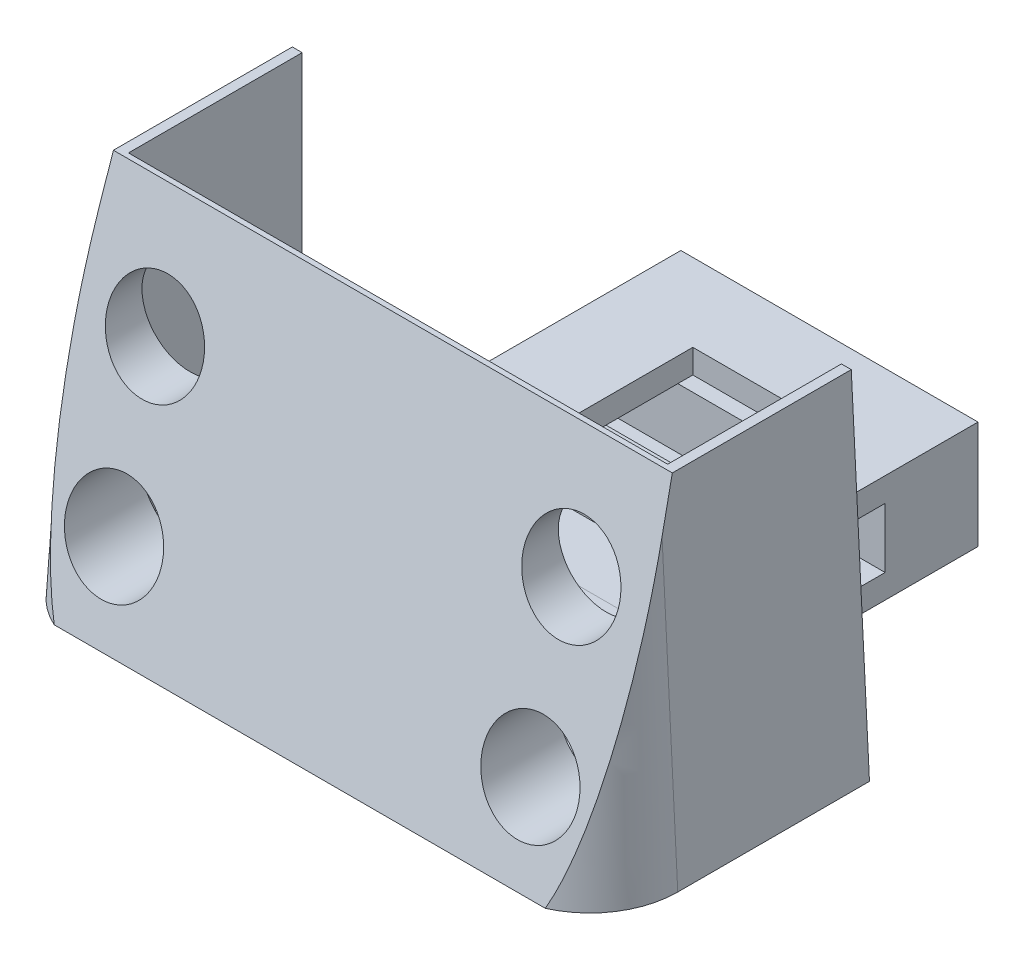
SolidWorks part; units mm, degrees
material "PLA (3D Printing)"
ref_plane "Front Plane" through (0, 0, 0) normal (0, 0, 1) x (1, 0, 0)
ref_plane "Top Plane" through (0, 0, 0) normal (0, 1, 0) x (1, 0, 0)
ref_plane "Right Plane" through (0, 0, 0) normal (1, 0, 0) x (0, 0, -1)
sketch "Sketch1" plane through (0, 0, 0) normal (0, 1, 0) x (1, 0, 0)
  line L0 (-35, 50) -> (35, 50)
  line L5 (50, 35) -> (50, -35)
  line L6 (-50, 35) -> (-50, -35)
  line L7 (-35, -50) -> (35, -50)
  arc A0 (35, -50) -> (50, -35) centre (35, -35) ccw
  arc A1 (-50, -35) -> (-35, -50) centre (-35, -35) ccw
  arc A2 (-50, 35) -> (-35, 50) centre (-35, 35) cw
  arc A3 (35, 50) -> (50, 35) centre (35, 35) cw
  point P14 (0, -50)
  point P19 (-50, 0)
  dimension "D3" = 15
  dimension "D4" = 15
  dimension "D5" = 15
  dimension "D6" = 15
  dimension "D1" = 100
  dimension "D2" = 100
extrude "Boss-Extrude1" add sketch "Sketch1" along normal blind 10
sketch "Sketch2" plane through (0, 10, 0) normal (0, 1, 0) x (1, 0, 0)
  line L0 (-50, 35) -> (-50, -35) construction
  line L1 (-42, 40) -> (-24.8, 40)
  line L2 (-42, 40) -> (-42, -3)
  line L3 (-42, -3) -> (-24.8, -3)
  line L4 (-24.8, 40) -> (-24.8, -3)
  line L5 (-42, 40) -> (-24.8, -3) construction
  line L6 (-42, -3) -> (-24.8, 40) construction
  line L7 (24.8, 40) -> (42, 40)
  line L8 (24.8, 40) -> (24.8, -3)
  line L9 (24.8, -3) -> (42, -3)
  line L10 (42, 40) -> (42, -3)
  line L11 (24.8, 40) -> (42, -3) construction
  line L12 (24.8, -3) -> (42, 40) construction
  line L13 (50, -35) -> (50, 35) construction
  line L15 (35, 50) -> (-35, 50) construction
  point P0 (-33.4, 18.5)
  point P5 (33.4, 18.5)
  dimension "D1" = 8
  dimension "D2" = 8
  dimension "D3" = 17.2
  dimension "D4" = 17.2
  dimension "D5" = 43
  dimension "D6" = 43
  dimension "D7" = 10
  dimension "D8" = 10
extrude "Cut-Extrude1" cut sketch "Sketch2" against normal through all
sketch "Sketch3" plane through (0, 10, 0) normal (0, 1, 0) x (1, 0, 0)
  line L1 (-40, -8) -> (40, -8)
  line L2 (-40, -8) -> (-40, -32)
  line L3 (-40, -32) -> (40, -32)
  line L4 (40, -8) -> (40, -32)
  line L5 (-40, -8) -> (40, -32) construction
  line L6 (-40, -32) -> (40, -8) construction
  line L7 (-45, -3) -> (45, -3)
  line L8 (-45, -3) -> (-45, -37)
  line L9 (-45, -37) -> (45, -37)
  line L10 (45, -3) -> (45, -37)
  line L11 (-45, -3) -> (45, -37) construction
  line L12 (-45, -37) -> (45, -3) construction
  line L13 (-35, -50) -> (35, -50) construction
  line L14 (-42, -3) -> (-24.8, -3) construction
  point P0 (0, -20)
  point P5 (0, -20)
  point P18 (0, -50)
  dimension "D1" = 24
  dimension "D2" = 80
  dimension "D3" = 34
  dimension "D4" = 90
extrude "Boss-Extrude3" add sketch "Sketch3" along normal blind 15
sketch "Sketch4" plane through (0, 10, 0) normal (0, 1, 0) x (1, 0, 0)
  line L0 (24.8, 40) -> (24.8, -3) construction
  line L3 (-24.8, 12.5) -> (24.8, 12.5)
  line L5 (-24.8, 24.5) -> (24.8, 24.5)
  line L6 (-24.8, 29.5) -> (24.8, 29.5)
  line L11 (-24.8, 7.5) -> (24.8, 7.5)
  line L12 (-24.8, 29.5) -> (-24.8, 24.5)
  line L13 (-24.8, -3) -> (-24.8, 40) construction
  line L14 (-24.8, 12.5) -> (-24.8, 7.5)
  line L15 (24.8, 12.5) -> (24.8, 7.5)
  line L16 (24.8, 29.5) -> (24.8, 24.5)
  point P4 (-24.8, 18.5)
  dimension "D1" = 5
  dimension "D2" = 12
  dimension "D3" = 5
  dimension "D4" = 6
extrude "Boss-Extrude4" add sketch "Sketch4" along normal blind 10
sketch "Sketch5" plane through (0, 20, 0) normal (0, 1, 0) x (1, 0, 0)
  line L0 (-24.8, 7.5) -> (24.8, 7.5) construction
  line L1 (-24.8, 29.5) -> (-9.8, 29.5)
  line L2 (-24.8, 29.5) -> (-24.8, 7.5)
  line L3 (-24.8, 7.5) -> (-9.8, 7.5)
  line L4 (-9.8, 29.5) -> (-9.8, 7.5)
  line L6 (24.8, 29.5) -> (9.8, 29.5)
  line L7 (24.8, 29.5) -> (24.8, 7.5)
  line L8 (24.8, 7.5) -> (9.8, 7.5)
  line L9 (9.8, 29.5) -> (9.8, 7.5)
  dimension "D1" = 15
  dimension "D2" = 15
extrude "Boss-Extrude5" add sketch "Sketch5" along normal blind 5
sketch "Sketch6" plane through (0, 10, 0) normal (0, 1, 0) x (1, 0, 0)
  line L1 (-45, -37) -> (45, -37)
  line L2 (-45, -37) -> (-45, 40)
  line L3 (-45, 40) -> (45, 40)
  line L4 (45, -37) -> (45, 40)
  line L5 (45, -37) -> (45, -3) construction
  line L6 (-24.8, 40) -> (-42, 40) construction
  line L7 (-50, 35) -> (-50, -35) construction
  line L8 (-35, -50) -> (35, -50) construction
  line L9 (50, -35) -> (50, 35) construction
  line L10 (35, 50) -> (-35, 50) construction
  line L11 (-50, 35) -> (-50, -35)
  line L12 (-35, -50) -> (35, -50)
  line L13 (50, -35) -> (50, 35)
  line L14 (35, 50) -> (-35, 50)
  arc A0 (-50, -35) -> (-35, -50) centre (-35, -35) ccw construction
  arc A1 (35, -50) -> (50, -35) centre (35, -35) ccw construction
  arc A2 (50, 35) -> (35, 50) centre (35, 35) ccw construction
  arc A3 (-35, 50) -> (-50, 35) centre (-35, 35) ccw construction
  arc A4 (-50, -35) -> (-35, -50) centre (-35, -35) ccw
  arc A5 (35, -50) -> (50, -35) centre (35, -35) ccw
  arc A6 (50, 35) -> (35, 50) centre (35, 35) ccw
  arc A7 (-35, 50) -> (-50, 35) centre (-35, 35) ccw
extrude "Boss-Extrude6" add sketch "Sketch6" along normal up to surface (15 mm away) up to face at (0, 25, 20)
sketch "Sketch9" plane through (0, 25, 0) normal (0, 1, 0) x (1, 0, 0)
  line L22 (-50, 35) -> (-50, -35) construction
  line L23 (-35, -50) -> (35, -50) construction
  line L24 (50, -35) -> (50, 35) construction
  line L25 (35, 50) -> (-35, 50) construction
  line L26 (-45, 35) -> (-45, -35)
  line L27 (-35, -45) -> (35, -45)
  line L28 (45, -35) -> (45, 35)
  line L29 (35, 45) -> (-35, 45)
  line L30 (-45, 35) -> (-45, -32)
  line L32 (45, -32) -> (45, 35)
  line L34 (-50, 35) -> (-50, -35)
  line L35 (-35, -50) -> (35, -50)
  line L36 (50, -35) -> (50, 35)
  line L37 (35, 50) -> (-35, 50)
  line L38 (45, -32) -> (-45, -32)
  line L39 (-40, -32) -> (40, -32) construction
  line L40 (43.6603, 40) -> (-43.6603, 40)
  line L41 (45, 40) -> (-45, 40) construction
  arc A23 (-50, -35) -> (-35, -50) centre (-35, -35) ccw construction
  arc A24 (35, -50) -> (50, -35) centre (35, -35) ccw construction
  arc A25 (50, 35) -> (35, 50) centre (35, 35) ccw construction
  arc A26 (-35, 50) -> (-50, 35) centre (-35, 35) ccw construction
  arc A27 (-45, -35) -> (-35, -45) centre (-35, -35) ccw
  arc A28 (35, -45) -> (45, -35) centre (35, -35) ccw
  arc A29 (45, 35) -> (35, 45) centre (35, 35) ccw
  arc A30 (-35, 45) -> (-45, 35) centre (-35, 35) ccw
  arc A33 (45, 35) -> (43.6603, 40) centre (35, 35) ccw
  arc A34 (-43.6603, 40) -> (-45, 35) centre (-35, 35) ccw
  arc A35 (-50, -35) -> (-35, -50) centre (-35, -35) ccw
  arc A36 (35, -50) -> (50, -35) centre (35, -35) ccw
  arc A37 (50, 35) -> (35, 50) centre (35, 35) ccw
  arc A38 (-35, 50) -> (-50, 35) centre (-35, 35) ccw
  dimension "D1" = 5
extrude "Boss-Extrude8" add sketch "Sketch9" along normal blind 39
chamfer "Chamfer1" distance 64 angle 3 8 edges at (0, 64, 50) (45.6066, 64, 45.6066) (-45.6066, 64, 45.6066) (50, 64, 0) (-50, 64, 0) (45.6066, 64, -45.6066) (-45.6066, 64, -45.6066) (0, 64, -50) first distance on face at (0, 32, 50) first distance on face at (44.0533, 32, 44.0533) first distance on face at (-44.0533, 32, 44.0533) first distance on face at (50, 32, 0) first distance on face at (-50, 32, 0) first distance on face at (44.0533, 32, -44.0533) first distance on face at (-44.0533, 32, -44.0533) first distance on face at (0, 32, -50)
chamfer "Chamfer3" distance 64 angle 12 1 edges at (0, 64, 46.6459) tangent propagation no first distance on face at (0, 32, 48.323)
sketch "Sketch17" plane through (0, 0, -29.5) normal (0, 0, -1) x (-1, 0, 0)
  line L8 (-9.8, 25) -> (-24.8, 25)
  line L9 (-24.8, 10) -> (24.8, 10)
  line L10 (-24.8, 10) -> (24.8, 10)
  line L11 (24.8, 10) -> (24.8, 25)
  line L12 (24.8, 25) -> (9.8, 25)
  line L13 (9.8, 25) -> (9.8, 20)
  line L14 (9.8, 20) -> (-9.8, 20)
  line L15 (-9.8, 20) -> (-9.8, 25)
  line L16 (-9.8, 25) -> (-24.8, 25)
  line L20 (24.8, 25) -> (9.8, 25)
  line L21 (9.8, 25) -> (9.8, 20)
  line L22 (9.8, 20) -> (-9.8, 20)
  line L23 (-9.8, 20) -> (-9.8, 25)
  line L24 (24.8, 10) -> (24.8, 25)
  line L25 (-24.8, 25) -> (-24.8, 10)
  line L26 (-24.8, 25) -> (-24.8, 10)
  dimension "D1" = 0
extrude "Cut-Extrude6" cut sketch "Sketch17" against normal blind 2.5
sketch "Sketch20" plane through (0, 25, 0) normal (0, -1, 0) x (1, 0, 0)
  line L0 (-45, -35) -> (-45, -40) construction
  line L1 (-45, -40) -> (-43.6603, -40) construction
  line L2 (45, -40) -> (45, -35) construction
  line L3 (43.6603, -40) -> (45, -40) construction
  line L4 (-45, -35) -> (-45, -40)
  line L5 (-45, -40) -> (-43.6603, -40)
  line L6 (45, -40) -> (45, -35)
  line L7 (43.6603, -40) -> (45, -40)
  arc A0 (-45, -35) -> (-43.6603, -40) centre (-35, -35) ccw construction
  arc A1 (43.6603, -40) -> (45, -35) centre (35, -35) ccw construction
  arc A2 (-45, -35) -> (-43.6603, -40) centre (-35, -35) ccw
  arc A3 (43.6603, -40) -> (45, -35) centre (35, -35) ccw
extrude "Cut-Extrude8" cut sketch "Sketch20" against normal blind 15
sketch "Sketch21" plane through (0, 25, 0) normal (0, 1, 0) x (1, 0, 0)
  line L4 (40, -8) -> (40, -32)
  line L6 (40, -8) -> (40, -32)
  line L8 (40, -32) -> (45, -32)
  line L10 (40, -32) -> (45, -32)
  line L24 (45, -32) -> (45, -3)
  line L25 (45, -32) -> (45, -3)
  line L26 (45, -3) -> (-45, -3)
  line L27 (45, -3) -> (-45, -3)
  line L28 (-45, -3) -> (-45, -32)
  line L29 (-45, -3) -> (-45, -32)
  line L30 (-45, -32) -> (-40, -32)
  line L31 (-45, -32) -> (-40, -32)
  line L32 (-40, -32) -> (-40, -8)
  line L33 (-40, -32) -> (-40, -8)
  line L34 (-40, -8) -> (40, -8)
  line L35 (-40, -8) -> (40, -8)
  dimension "D1" = 0
extrude "Cut-Extrude9" cut sketch "Sketch21" against normal up to surface (15 mm away) up to face at (0, 10, 20)
sketch "Sketch22" plane through (0, 0, 0) normal (0, -1, 0) x (1, 0, 0)
  line L0 (-35, 50) -> (35, 50) construction
  line L1 (-15, 32) -> (15, 32)
  line L2 (-15, 32) -> (-15, 25)
  line L3 (-15, 25) -> (15, 25)
  line L4 (15, 32) -> (15, 25)
  line L5 (24.8, 3) -> (42, 3) construction
  line L7 (0, 50) -> (0, -50) construction
  line L8 (35, -50) -> (-35, -50) construction
  point P12 (0, 32)
  dimension "D1" = 18
  dimension "D2" = 22
  dimension "D3" = 30
extrude "Cut-Extrude10" cut sketch "Sketch22" against normal up to surface (10 mm away) up to face at (0, 10, -18.5)
sketch "Sketch25" plane through (0, 0, 32) normal (0, 0, -1) x (-1, 0, 0)
  line L0 (-15, 10) -> (-45, 10) construction
  line L1 (45, 10) -> (15, 10) construction
  line L2 (-45, 64) -> (-45, 10) construction
  line L3 (45, 64) -> (45, 10) construction
  circle A0 centre (-34.75, 45.5) radius 8
  circle A1 centre (34.75, 45.5) radius 8
  circle A2 centre (-34.75, 20) radius 8
  circle A3 centre (34.75, 20) radius 8
  dimension "D3" = 16
  dimension "D4" = 16
  dimension "D5" = 16
  dimension "D6" = 16
  dimension "D9" = 10.25
  dimension "D1" = 25.5
  dimension "D2" = 25.5
  dimension "D7" = 10
  dimension "D8" = 10
  dimension "D10" = 10.25
extrude "Cut-Extrude19" cut sketch "Sketch25" against normal through all
sketch "Sketch29" plane through (0, 10, 0) normal (0, 1, 0) x (1, 0, 0)
  line L1 (-24, -3) -> (-15, -3)
  line L2 (-24, -3) -> (-24, -32)
  line L3 (-24, -32) -> (-15, -32)
  line L4 (-15, -3) -> (-15, -32)
  line L5 (15, -32) -> (24, -32)
  line L6 (15, -32) -> (15, -3)
  line L7 (15, -3) -> (24, -3)
  line L8 (24, -32) -> (24, -3)
  line L9 (-45, 40) -> (-45, -32) construction
  line L10 (45, -32) -> (45, 40) construction
  line L11 (-24.8, -3) -> (-42, -3) construction
  line L12 (42, -3) -> (24.8, -3) construction
  line L13 (-45, -32) -> (45, -32) construction
  dimension "D1" = 21
  dimension "D2" = 21
  dimension "D3" = 9
  dimension "D4" = 9
extrude "Boss-Extrude10" add sketch "Sketch29" along normal blind 28
sketch "Sketch31" plane through (0, 10, 0) normal (0, 1, 0) x (1, 0, 0)
  line L4 (24.8, 27) -> (24.8, 40)
  line L6 (24.8, 27) -> (24.8, 40)
  line L13 (24.8, 40) -> (-24.8, 40)
  line L15 (24.8, 40) -> (-24.8, 40)
  line L17 (-24.8, 40) -> (-24.8, 27)
  line L18 (-24.8, 40) -> (-24.8, 27)
  line L19 (-24.8, 27) -> (24.8, 27)
  line L21 (-24.8, 27) -> (24.8, 27)
  dimension "D1" = 0
extrude "Boss-Extrude12" add sketch "Sketch31" along normal up to surface (28 mm away) up to face at (-19.5, 38, 17.5)
sketch "Sketch30" plane through (0, 38, 0) normal (0, 1, 0) x (1, 0, 0)
  line L1 (-24.8, 36) -> (24.8, 36)
  line L2 (-24.8, 36) -> (-24.8, 40)
  line L3 (-24.8, 40) -> (24.8, 40)
  line L11 (-24, -3) -> (-24, -32) construction
  line L12 (-24, -22) -> (24, -22)
  line L13 (-24, -22) -> (-24, -18)
  line L14 (-24, -18) -> (24, -18)
  line L15 (24, -22) -> (24, -18)
  line L16 (24, -3) -> (24, -32) construction
  line L21 (43.6603, 40) -> (-43.6603, 40) construction
  line L22 (-24.8, 40) -> (-24.8, 27) construction
  line L23 (24.8, 40) -> (24.8, 36)
  line L24 (24.8, 27) -> (24.8, 40) construction
  dimension "D1" = 54
  dimension "D2" = 4
  dimension "D3" = 4
extrude "Boss-Extrude11" add sketch "Sketch30" along normal blind 10
sketch "Sketch33" plane through (0, 25, 0) normal (0, 1, 0) x (1, 0, 0)
  line L0 (24.8, 27) -> (9.8, 27) construction
  line L1 (9.8, 27) -> (9.8, 7.5) construction
  line L2 (9.8, 7.5) -> (24.8, 7.5) construction
  line L3 (24.8, 7.5) -> (24.8, 27) construction
  line L4 (-9.8, 7.5) -> (-9.8, 27) construction
  line L5 (-9.8, 27) -> (-24.8, 27) construction
  line L6 (-24.8, 27) -> (-24.8, 7.5) construction
  line L7 (-24.8, 7.5) -> (-9.8, 7.5) construction
  line L8 (24.8, 27) -> (9.8, 27)
  line L9 (9.8, 27) -> (9.8, 7.5)
  line L10 (9.8, 7.5) -> (24.8, 7.5)
  line L11 (24.8, 7.5) -> (24.8, 27)
  line L12 (-9.8, 7.5) -> (-9.8, 27)
  line L13 (-9.8, 27) -> (-24.8, 27)
  line L14 (-24.8, 27) -> (-24.8, 7.5)
  line L15 (-24.8, 7.5) -> (-9.8, 7.5)
extrude "Boss-Extrude13" add sketch "Sketch33" along normal up to surface (13 mm away) up to face at (0, 38, -31.5)
sketch "Sketch23" plane through (0, 10, 0) normal (0, 1, 0) x (1, 0, 0)
  line L1 (-15, -3) -> (15, -3)
  line L2 (-15, -3) -> (-15, -31.9954)
  line L3 (-15, -31.9954) -> (15, -31.9954)
  line L4 (15, -3) -> (15, -31.9954)
  line L6 (0, 50) -> (0, -49.9954) construction
  line L8 (35, -49.9954) -> (-35, -49.9954) construction
  line L12 (35, 50) -> (-35, 50) construction
  line L13 (24, -3) -> (15, -3) construction
  point P8 (0, -3)
  dimension "D2" = 30
  dimension "D3" = 18
extrude "Cut-Extrude17" cut sketch "Sketch23" against normal blind 5
sketch "Sketch34" plane through (0, 10, 0) normal (0, 1, 0) x (1, 0, 0)
  line L1 (-24.8, -3) -> (-15, -3)
  line L2 (-24.8, -3) -> (-24.8, 7.5)
  line L3 (-24.8, 7.5) -> (-15, 7.5)
  line L4 (-15, -3) -> (-15, 7.5)
  line L5 (-24.8, 7.5) -> (24.8, 7.5) construction
  line L6 (24.8, -3) -> (15, -3)
  line L7 (24.8, -3) -> (24.8, 7.5)
  line L8 (24.8, 7.5) -> (15, 7.5)
  line L9 (15, -3) -> (15, 7.5)
  line L10 (-24.8, 7.5) -> (-9.8, 7.5) construction
  line L11 (-15, -18) -> (-15, -3) construction
  line L12 (15, -25) -> (15, -3) construction
extrude "Boss-Extrude14" add sketch "Sketch34" along normal up to surface (28 mm away) up to face at (-19.5, 38, 10.5)
sketch "Sketch35" plane through (0, 10, 0) normal (0, 1, 0) x (1, 0, 0)
  line L4 (15, -3) -> (15, 7.5)
  line L6 (15, -3) -> (15, 7.5)
  line L12 (15, 7.5) -> (-15, 7.5)
  line L14 (15, 7.5) -> (-15, 7.5)
  line L16 (-15, 7.5) -> (-15, -3)
  line L17 (-15, 7.5) -> (-15, -3)
  line L18 (-15, -3) -> (15, -3)
  line L19 (-15, -3) -> (15, -3)
  dimension "D1" = 0
extrude "Cut-Extrude22" cut sketch "Sketch35" against normal up to surface (5 mm away) up to face at (0, 5, 14)
sketch "Sketch37" plane through (0, 5, 0) normal (0, 1, 0) x (1, 0, 0)
  line L4 (-15, -25) -> (15, -25)
  line L5 (15, -25) -> (15, 7.5)
  line L6 (15, 7.5) -> (-15, 7.5)
  line L7 (-15, 7.5) -> (-15, -25)
  line L8 (-15, -25) -> (15, -25)
  line L9 (15, -25) -> (15, 7.5)
  line L10 (15, 7.5) -> (-15, 7.5)
  line L11 (-15, 7.5) -> (-15, -25)
  dimension "D1" = 0
extrude "Boss-Extrude15" add sketch "Sketch37" along normal blind 5
sketch "Sketch38" plane through (0, 64, 0) normal (0, 1, 0) x (1, 0, 0)
  line L0 (43.6603, 40) -> (-43.6603, 40) construction
  line L1 (-50, 60) -> (50, 60)
  line L2 (-50, 60) -> (-50, 40)
  line L3 (-50, 40) -> (50, 40)
  line L4 (50, 60) -> (50, 40)
  line L5 (-50, 35) -> (-50, -35) construction
  line L6 (50, -35) -> (50, 35) construction
  dimension "D1" = 20
extrude "Cut-Extrude23" cut sketch "Sketch38" against normal up to surface (64 mm away) up to face at (0, 0, 28.5)
sketch "Sketch39" plane through (0, 0, 0) normal (0, -1, 0) x (1, 0, 0)
  line L0 (-50, -35) -> (-50, 35) construction
  line L1 (-42, 3) -> (-50, 3)
  line L2 (-42, 3) -> (-42, -40)
  line L3 (-42, -40) -> (-50, -40)
  line L4 (-50, 3) -> (-50, -40)
  line L5 (-49.1421, -40) -> (-42, -40) construction
  line L6 (0, 50) -> (0, -40) construction
  line L7 (-35, 50) -> (35, 50) construction
  line L8 (-24.8, -40) -> (24.8, -40) construction
  line L9 (42, -40) -> (50, -40)
  line L10 (50, 3) -> (50, -40)
  line L11 (42, 3) -> (50, 3)
  line L12 (42, 3) -> (42, -40)
extrude "Cut-Extrude24" cut sketch "Sketch39" against normal up to surface (64 mm away) up to face at (0, 64, -14.2135)
sketch "Sketch40" plane through (-24, 0, 0) normal (-1, 0, 0) x (0, 0, 1)
  line L0 (3, 38) -> (3, 10) construction
  line L1 (6, 35) -> (29, 35)
  line L2 (6, 35) -> (6, 13)
  line L3 (6, 13) -> (29, 13)
  line L4 (29, 35) -> (29, 13)
  line L5 (3, 38) -> (18, 38) construction
  line L6 (32, 38) -> (32, 10) construction
  line L7 (3, 10) -> (32, 10) construction
  dimension "D1" = 3
  dimension "D2" = 3
  dimension "D3" = 3
  dimension "D4" = 3
extrude "Cut-Extrude25" cut sketch "Sketch40" against normal up to surface (48 mm away)
sketch "Sketch41" plane through (0, 0, 22) normal (0, 0, 1) x (1, 0, 0)
  line L6 (-24, 38) -> (-15, 38)
  line L7 (-15, 38) -> (15, 38)
  line L8 (15, 38) -> (24, 38)
  line L9 (24, 38) -> (24, 48)
  line L10 (24, 48) -> (-24, 48)
  line L11 (-24, 48) -> (-24, 38)
  line L12 (-24, 38) -> (-15, 38)
  line L13 (-15, 38) -> (15, 38)
  line L14 (15, 38) -> (24, 38)
  line L15 (24, 38) -> (24, 48)
  line L16 (24, 48) -> (-24, 48)
  line L17 (-24, 48) -> (-24, 38)
  dimension "D1" = 0
extrude "Cut-Extrude26" cut sketch "Sketch41" against normal up to surface (62 mm away) up to face at (0, 24, -40)
sketch "Sketch42" plane through (0, 38, 0) normal (0, 1, 0) x (1, 0, 0)
  line L1 (-24, -3) -> (24, -3)
  line L2 (-24, -3) -> (-24, -32)
  line L3 (-24, -32) -> (24, -32)
  line L4 (24, -3) -> (24, -32)
extrude "Cut-Extrude27" cut sketch "Sketch42" against normal up to surface (28 mm away) up to face at (0, 10, -18.5)
sketch "Sketch43" plane through (24.8, 0, 0) normal (1, 0, 0) x (0, 0, -1)
  line L0 (24.5, 10) -> (12.5, 10) construction
  line L1 (40, 0) -> (-50, 0)
  line L2 (40, 0) -> (40, 6)
  line L3 (40, 6) -> (-50, 6)
  line L4 (-50, 0) -> (-50, 6)
  dimension "D1" = 4
extrude "Cut-Extrude28" cut sketch "Sketch43" against normal through all and the other way through all
sketch "Sketch44" plane through (24.8, 0, 0) normal (1, 0, 0) x (0, 0, -1)
  line L0 (-3, 38) -> (-3, 10) construction
  line L1 (40, 48) -> (-3, 48)
  line L2 (40, 48) -> (40, 24)
  line L3 (40, 24) -> (-3, 24)
  line L4 (-3, 48) -> (-3, 24)
  line L5 (12.5, 20) -> (24.5, 20) construction
  dimension "D1" = 4
extrude "Cut-Extrude29" cut sketch "Sketch44" against normal through all and the other way through all
sketch "Sketch45" plane through (0, 10, 0) normal (0, 1, 0) x (1, 0, 0)
  line L1 (15, -25) -> (-15, -25)
  line L2 (15, -25) -> (15, -32)
  line L3 (15, -32) -> (-15, -32)
  line L4 (-15, -25) -> (-15, -32)
extrude "Boss-Extrude16" add sketch "Sketch45" against normal up to surface (4 mm away) up to face at (0, 6, 10.1398)
sketch "Sketch46" plane through (0, 24, 0) normal (0, 1, 0) x (1, 0, 0)
  line L0 (-24.8, -3) -> (-24.8, 40) construction
  line L1 (24.8, -3) -> (-24.8, -3)
  line L2 (24.8, -3) -> (24.8, 7.5)
  line L3 (24.8, 7.5) -> (-24.8, 7.5)
  line L4 (-24.8, -3) -> (-24.8, 7.5)
  line L5 (-9.8, 7.5) -> (-15, 7.5) construction
extrude "Cut-Extrude30" cut sketch "Sketch46" against normal up to surface (14 mm away) up to face at (0, 10, -18.5)
sketch "Sketch47" plane through (0, 10, 0) normal (0, 1, 0) x (1, 0, 0)
  line L0 (-24.8, -3) -> (24.8, -3)
split "Split1" trim tools "Sketch47" bodies to split 146 resulting bodies 147 148
